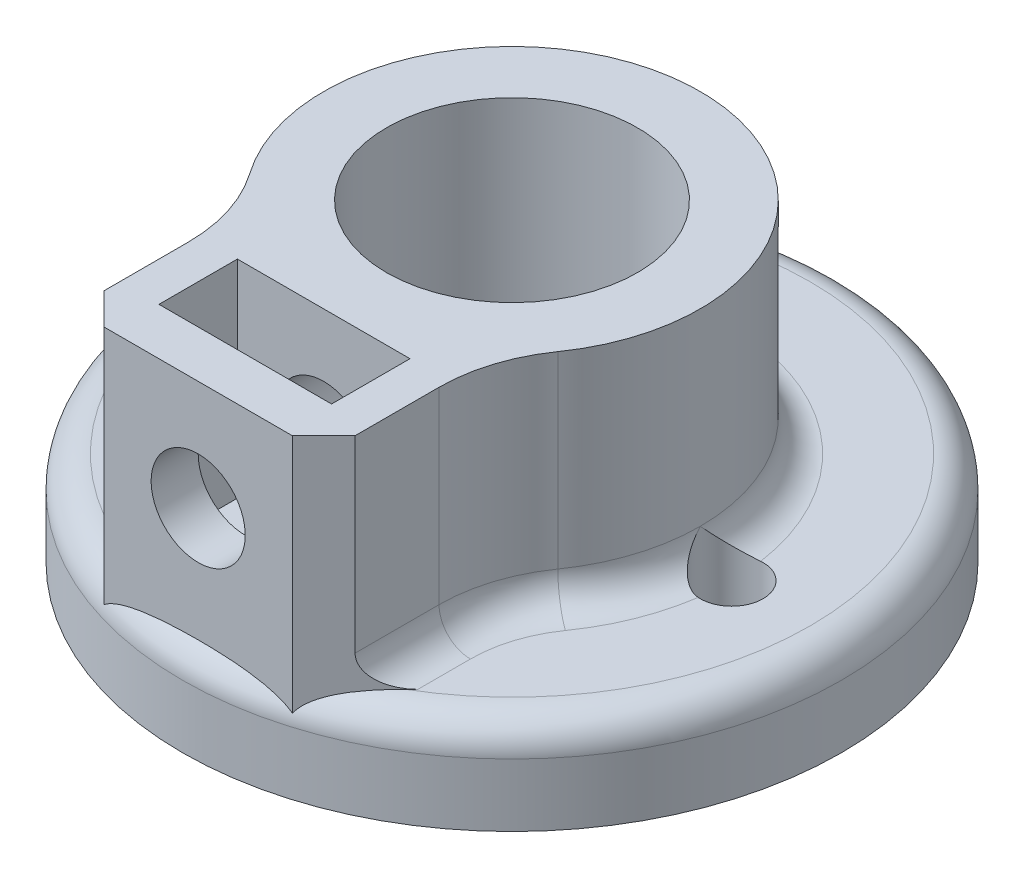
SolidWorks part; units mm, degrees
ref_plane "Front Plane" through (0, 0, 0) normal (0, 0, 1) x (1, 0, 0)
ref_plane "Top Plane" through (0, 0, 0) normal (0, 1, 0) x (1, 0, 0)
ref_plane "Right Plane" through (0, 0, 0) normal (1, 0, 0) x (0, 0, -1)
sketch "Sketch1" plane through (0, 0, 0) normal (0, 1, 0) x (1, 0, 0)
  circle A0 centre (0, 0) radius 10.5
  circle A1 centre (0, 7) radius 1
  circle A2 centre (7, 0) radius 1
  circle A3 centre (0, -7) radius 1
  circle A4 centre (-7, 0) radius 1
  circle A5 centre (0, 0) radius 4
  dimension "D1" = 21
  dimension "D2" = 2
  dimension "D5" = 8
  dimension "D3" = 7
  dimension "D4" = 4
extrude "Boss-Extrude1" add sketch "Sketch1" along normal blind 3
sketch "Sketch2" plane through (0, 3, 0) normal (0, 1, 0) x (1, 0, 0)
  circle A0 centre (0, 0) radius 4 construction
  circle A1 centre (0, 0) radius 4
  circle A2 centre (0, 0) radius 6
  dimension "D1" = 12
extrude "Boss-Extrude2" add sketch "Sketch2" along normal blind 7
sketch "Sketch5" plane through (0, 10, 0) normal (0, 1, 0) x (1, 0, 0)
  line L0 (0, -6) -> (0, -10) construction
  line L2 (-4, -5) -> (-4, -4.4721)
  line L3 (4, -5) -> (4, -4.4721)
  line L4 (-4, -10) -> (4, -10)
  line L5 (-4, -10) -> (-4, -5)
  line L6 (4, -10) -> (4, -5)
  circle A1 centre (0, 0) radius 6
  arc A2 (-4, -4.4721) -> (4, -4.4721) centre (0, 0) ccw
  point P7 (0, -5)
  dimension "D2" = 8
  dimension "D3" = 4
  dimension "D1" = 0
extrude "Boss-Extrude3" add sketch "Sketch5" against normal up to surface (7 mm away) up to face at (0, 3, 0.5)
sketch "Sketch6" plane through (0, 0, 0) normal (0, -1, 0) x (1, 0, 0)
  circle A0 centre (0, 7) radius 1 construction
  circle A1 centre (0, 7) radius 1
extrude "Boss-Extrude4" add sketch "Sketch6" against normal up to surface (3 mm away) up to face at (0, 3, -0.3906)
sketch "Sketch7" plane through (0, 10, 0) normal (0, 1, 0) x (1, 0, 0)
  line L0 (0, -4) -> (0, -10) construction
  line L1 (3.2016, -10) -> (-3.2016, -10) construction
  line L3 (-4, -10) -> (4, -10) construction
  line L5 (-2.75, -6) -> (2.75, -6)
  line L6 (-2.75, -6) -> (-2.75, -8.5)
  line L7 (-2.75, -8.5) -> (2.75, -8.5)
  line L8 (2.75, -6) -> (2.75, -8.5)
  circle A0 centre (0, 0) radius 4 construction
  circle A1 centre (0, 0) radius 4 construction
  dimension "D1" = 6
  dimension "D4" = 2.5
  dimension "D2" = 5.5
  dimension "D3" = 2.75
  dimension "D5" = 1.5
extrude "Cut-Extrude2" cut sketch "Sketch7" against normal blind 6.6
sketch "Sketch4" plane through (0, 0, 0) normal (0, 0, 1) x (1, 0, 0)
  line L0 (-6, 10) -> (-6, 3) construction
  line L1 (-6, 10) -> (-6, 3)
  line L2 (-6, 6.5) -> (6, 6.5) construction
  line L3 (6, 3) -> (6, 10) construction
  circle A0 centre (0, 6.5) radius 1.5
  dimension "D1" = 3
  dimension "D2" = 7
extrude "Cut-Extrude1" cut sketch "Sketch4" along normal through all contours A0 L2 | L2 A0 region at (0, 7.1366, 0) region at (0, 5.8634, 0)
chamfer "Chamfer1" distance 1 angle 45 2 edges at (4, 6.5, 10) (-4, 6.5, 10)
fillet "Fillet1" radius 5 2 edges at (-4, 6.5, 4.4721) (4, 6.5, 4.4721)
fillet "Fillet2" radius 1 8 edges at (4, 3, 7.6623) (4.2327, 3, 4.817) (5.7208, 3, 1.8091) (-5.7208, 3, 1.8091) (4.2426, 3, -4.2426) (-4.2426, 3, -4.2426) (-4, 3, 7.6623) (-4.2327, 3, 4.817)
fillet "Fillet3" radius 1 1 edges at (0, 3, 10.5)
